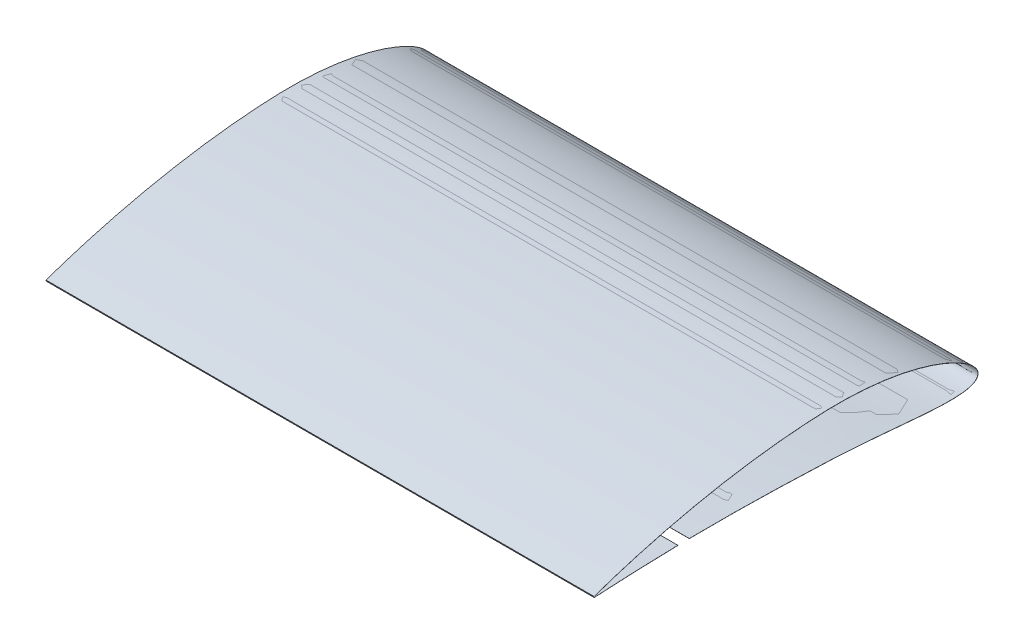
SolidWorks part; units mm, degrees
material "E-Glass Fiber Real"
ref_plane "Front Plane" through (0, 0, 0) normal (0, 0, 1) x (1, 0, 0)
ref_plane "Top Plane" through (0, 0, 0) normal (0, 1, 0) x (1, 0, 0)
ref_plane "Right Plane" through (0, 0, 0) normal (1, 0, 0) x (0, 0, -1)
curve "Curve1"
  spline degree 3 poles (0, 0.0012, 1.0003) (0, 0.0015, 0.9994) (0, 0.0028, 0.9958) (0, 0.0055, 0.9879) (0, 0.0099, 0.9747) (0, 0.0159, 0.9565) (0, 0.0233, 0.9333) (0, 0.0318, 0.9054) (0, 0.0411, 0.8731) (0, 0.051, 0.8366) (0, 0.0612, 0.7964) (0, 0.0713, 0.7528) (0, 0.0811, 0.7063) (0, 0.0903, 0.6574) (0, 0.0985, 0.6067) (0, 0.1057, 0.5546) (0, 0.1115, 0.5018) (0, 0.1158, 0.4488) (0, 0.1186, 0.3959) (0, 0.1189, 0.3436) (0, 0.1164, 0.2927) (0, 0.1112, 0.2442) (0, 0.1037, 0.1988) (0, 0.0942, 0.157) (0, 0.0831, 0.1194) (0, 0.0711, 0.0865) (0, 0.0584, 0.0585) (0, 0.0457, 0.0357) (0, 0.0334, 0.0184) (0, 0.0218, 0.0064) (0, 0.0108, -0.0005) (0, -0.0003, -0.0011) (0, -0.0092, 0.0055) (0, -0.0148, 0.017) (0, -0.0185, 0.0329) (0, -0.0204, 0.0533) (0, -0.0208, 0.0781) (0, -0.0198, 0.107) (0, -0.0176, 0.1398) (0, -0.0147, 0.176) (0, -0.0111, 0.2153) (0, -0.0074, 0.2574) (0, -0.0037, 0.3019) (0, -0.0005, 0.3484) (0, 0.002, 0.397) (0, 0.0037, 0.4471) (0, 0.0055, 0.4983) (0, 0.0069, 0.5496) (0, 0.0079, 0.6006) (0, 0.0085, 0.6505) (0, 0.0086, 0.699) (0, 0.0083, 0.7455) (0, 0.0076, 0.7894) (0, 0.0065, 0.8302) (0, 0.0053, 0.8675) (0, 0.0039, 0.9007) (0, 0.0027, 0.9296) (0, 0.0013, 0.9539) (0, 0.0006, 0.9727) (0, -0.0011, 0.9872) (0, 0, 0.9944) (0, -0.002, 0.9999) (0, -0.0005, 1) (0, 0, 1) knots 0 0 0 0 0.001372 0.005465 0.012235 0.021602 0.033461 0.047671 0.064081 0.082496 0.102719 0.124527 0.147676 0.171913 0.196978 0.222597 0.248497 0.274385 0.300041 0.32569 0.350525 0.37428 0.396711 0.417577 0.436654 0.453744 0.46868 0.481329 0.491631 0.499616 0.505546 0.510185 0.514824 0.520702 0.528516 0.538466 0.550543 0.564643 0.580638 0.598345 0.617584 0.638174 0.659922 0.682632 0.706121 0.730727 0.7557 0.780732 0.805564 0.829932 0.85357 0.876213 0.89761 0.917519 0.935698 0.951943 0.966047 0.97784 0.987174 0.993932 0.998018 0.999386 1 1 1 1
sketch "Sketch1" plane through (0, 0, 0) normal (1, 0, 0) x (0, 0, -1)
  line L0 (-354.7873, -0.0303) -> (-354.8762, 0.4104)
  line L1 (-354.7873, -0.0303) -> (0.8093, 1.5275) construction
  line L2 (0.8093, 1.5275) -> (0.7921, 5.4415) construction
  line L3 (-354.8867, -0.0431) -> (-354.9915, 0.4765)
  spline S0 degree 1 poles (-354.9915, 0.4765) (-354.8867, -0.0431) knots 0 0 1 1 construction
  spline S1 degree 3 poles (-354.8762, 0.4104) (-354.5599, 0.5194) (-353.2997, 0.9536) (-350.4787, 1.9271) (-345.801, 3.4978) (-336.0241, 6.7216) (-319.6545, 11.7989) (-300.5983, 17.1306) (-282.4229, 21.7243) (-261.1758, 26.6516) (-238.6223, 31.1455) (-208.7748, 36.0048) (-183.9617, 39.0905) (-158.9023, 41.1132) (-140.0967, 42.1114) (-121.5167, 42.2289) (-103.4222, 41.3211) (-86.1884, 39.4787) (-70.0435, 36.8105) (-55.1998, 33.4329) (-41.8434, 29.5109) (-30.1305, 25.2201) (-20.187, 20.7343) (-12.1072, 16.2263) (-5.9269, 11.8553) (-1.6792, 7.7165) (0.7658, 3.7968) (0.9875, -0.1483) (-1.3511, -3.3089) (-5.4508, -5.2881) (-11.0873, -6.5875) (-18.3491, -7.2685) (-27.1638, -7.4049) (-37.4471, -7.0538) (-49.0831, -6.3019) (-61.9524, -5.238) (-75.9299, -3.9839) (-96.4067, -2.1536) (-117.9372, -0.4584) (-140.4848, 0.6745) (-158.2965, 1.2867) (-176.4839, 1.9179) (-200.672, 2.5862) (-224.5411, 2.9791) (-247.8302, 3.0285) (-264.3373, 2.9074) (-279.9331, 2.6564) (-294.438, 2.2829) (-307.6819, 1.8521) (-319.5134, 1.3711) (-329.7674, 0.9129) (-338.3889, 0.4268) (-345.077, 0.1915) (-350.2276, -0.4064) (-352.7802, -0.0354) (-354.7446, -0.7581) (-354.7772, -0.2025) (-354.7873, -0.0303) knots 0 0 0 0 0.001372 0.005465 0.012235 0.021602 0.047671 0.082496 0.102719 0.124527 0.171913 0.196978 0.248497 0.274385 0.300041 0.32569 0.350525 0.37428 0.396711 0.417577 0.436654 0.453744 0.46868 0.481329 0.491631 0.499616 0.505546 0.510185 0.514824 0.520702 0.528516 0.538466 0.550543 0.564643 0.580638 0.598345 0.617584 0.638174 0.682632 0.706121 0.730727 0.7557 0.780732 0.829932 0.85357 0.876213 0.89761 0.917519 0.935698 0.951943 0.966047 0.97784 0.987174 0.993932 0.998018 0.999386 1 1 1 1
  spline S2 degree 3 poles (-354.9915, 0.4765) (-347.7836, 2.9597) (-333.3117, 7.7674) (-304.0781, 16.465) (-267.0965, 25.7748) (-229.6395, 32.9445) (-199.4502, 37.3012) (-176.7143, 39.8272) (-153.9062, 41.5865) (-131.0398, 42.4798) (-108.1542, 41.8638) (-89.1681, 39.9795) (-74.0989, 37.5944) (-62.8814, 35.3319) (-51.7773, 32.562) (-40.8241, 29.2405) (-31.8676, 25.9544) (-24.8509, 22.952) (-19.6856, 20.4844) (-14.6455, 17.7675) (-9.7758, 14.742) (-5.9468, 11.8749) (-3.1406, 9.2694) (-1.2444, 7.1001) (0.0802, 5.0591) (0.7347, 3.2254) (0.9597, 1.7496) (0.8529, 0.2733) (0.1431, -1.5595) (-1.5772, -3.4176) (-4.1427, -4.7763) (-6.8851, -5.694) (-9.6819, -6.3305) (-13.4588, -6.9198) (-18.2203, -7.308) (-23.9414, -7.4643) (-29.6625, -7.4093) (-35.3792, -7.2116) (-41.0906, -6.9122) (-48.6991, -6.4144) (-58.1991, -5.6579) (-69.5902, -4.656) (-80.9786, -3.6301) (-92.3689, -2.6278) (-107.5631, -1.3754) (-126.5734, -0.0489) (-145.6132, 0.7575) (-160.8504, 1.2747) (-176.0872, 1.8014) (-195.1363, 2.3454) (-218.0008, 2.7794) (-237.057, 2.9256) (-252.3023, 2.8969) (-263.736, 2.8025) (-275.1687, 2.638) (-286.6002, 2.3917) (-296.1246, 2.1237) (-303.7428, 1.8773) (-309.4566, 1.6726) (-315.1707, 1.4473) (-320.8814, 1.2068) (-326.5862, 0.9549) (-331.3522, 0.7146) (-335.168, 0.5116) (-338.021, 0.3672) (-340.8524, 0.247) (-343.6848, 0.1184) (-346.0992, -0.0683) (-348.0577, -0.2494) (-349.4952, -0.3431) (-350.6418, -0.3458) (-351.5091, -0.2914) (-352.1695, -0.2751) (-352.8786, -0.3248) (-353.5347, -0.4594) (-354.1336, -0.6434) (-354.4711, -0.6994) (-354.7188, -0.6206) (-354.8778, -0.3922) (-354.8788, -0.1783) (-354.8867, -0.0431) knots -0.00012 -0.00012 -0.00012 -0.00012 0.031134 0.062387 0.124894 0.187401 0.218655 0.249908 0.281162 0.312415 0.343669 0.374922 0.390549 0.406176 0.421802 0.437429 0.453056 0.460869 0.468683 0.476496 0.484309 0.492123 0.496029 0.499936 0.503843 0.505796 0.507749 0.509703 0.511656 0.515563 0.519469 0.523376 0.527283 0.53119 0.539003 0.546816 0.55463 0.562443 0.570256 0.57807 0.593696 0.609323 0.62495 0.640577 0.656203 0.687457 0.71871 0.734337 0.749964 0.781217 0.812471 0.843724 0.859351 0.874978 0.890604 0.906231 0.921858 0.929671 0.937485 0.945298 0.953111 0.960925 0.968738 0.972645 0.976552 0.980458 0.984365 0.988272 0.990225 0.992178 0.994132 0.995108 0.996085 0.997062 0.998038 0.998527 0.999015 0.999259 0.999503 0.999992 0.999992 0.999992 0.999992
  dimension "D1" = 355.6
  dimension "D2" = 0.1
extrude "Boss-Extrude1" add sketch "Sketch1" along normal blind 254 and the other way blind 254
sketch "Sketch2" plane through (0, 0, 0) normal (1, 0, 0) x (0, 0, -1)
  line L0 (-266.7, 25.311) -> (-266.7, -28.097)
  line L1 (0, 38.2128) -> (0, -38.2128) construction
  line L2 (-266.7, 25.311) -> (-291.6046, -28.097)
  line L3 (-291.6046, -28.097) -> (-266.7, -28.097)
  spline S0 degree 3 poles (-354.7873, -0.0303) (-354.7772, -0.2025) (-354.7446, -0.7581) (-352.7802, -0.0354) (-350.2276, -0.4064) (-345.077, 0.1915) (-338.3889, 0.4268) (-329.7674, 0.9129) (-319.5134, 1.3711) (-307.6819, 1.8521) (-294.438, 2.2829) (-279.9331, 2.6564) (-264.3373, 2.9074) (-247.8302, 3.0285) (-224.5411, 2.9791) (-200.672, 2.5862) (-176.4839, 1.9179) (-158.2965, 1.2867) (-140.4848, 0.6745) (-117.9372, -0.4584) (-96.4067, -2.1536) (-75.9299, -3.9839) (-61.9524, -5.238) (-49.0831, -6.3019) (-37.4471, -7.0538) (-27.1638, -7.4049) (-18.3491, -7.2685) (-11.0873, -6.5875) (-5.4508, -5.2881) (-1.3511, -3.3089) (0.9875, -0.1483) (0.7658, 3.7968) (-1.6792, 7.7165) (-5.9269, 11.8553) (-12.1072, 16.2263) (-20.187, 20.7343) (-30.1305, 25.2201) (-41.8434, 29.5109) (-55.1998, 33.4329) (-70.0435, 36.8105) (-86.1884, 39.4787) (-103.4222, 41.3211) (-121.5167, 42.2289) (-140.0967, 42.1114) (-158.9023, 41.1132) (-183.9617, 39.0905) (-208.7748, 36.0048) (-238.6223, 31.1455) (-261.1758, 26.6516) (-282.4229, 21.7243) (-300.5983, 17.1306) (-319.6545, 11.7989) (-336.0241, 6.7216) (-345.801, 3.4978) (-350.4787, 1.9271) (-353.2997, 0.9536) (-354.5599, 0.5194) (-354.8762, 0.4104) knots 0 0 0 0 0.000614 0.001982 0.006068 0.012826 0.02216 0.033953 0.048057 0.064302 0.082481 0.10239 0.123787 0.14643 0.170068 0.219268 0.2443 0.269273 0.293879 0.317368 0.361826 0.382416 0.401655 0.419362 0.435357 0.449457 0.461534 0.471484 0.479298 0.485176 0.489815 0.494454 0.500384 0.508369 0.518671 0.53132 0.546256 0.563346 0.582423 0.603289 0.62572 0.649475 0.67431 0.699959 0.725615 0.751503 0.803022 0.828087 0.875473 0.897281 0.917504 0.952329 0.978398 0.987765 0.994535 0.998628 1 1 1 1 construction
  dimension "D1" = 266.7
  dimension "D2" = 25
extrude "Cut-Extrude1" cut sketch "Sketch2" against normal through all both and the other way through all
